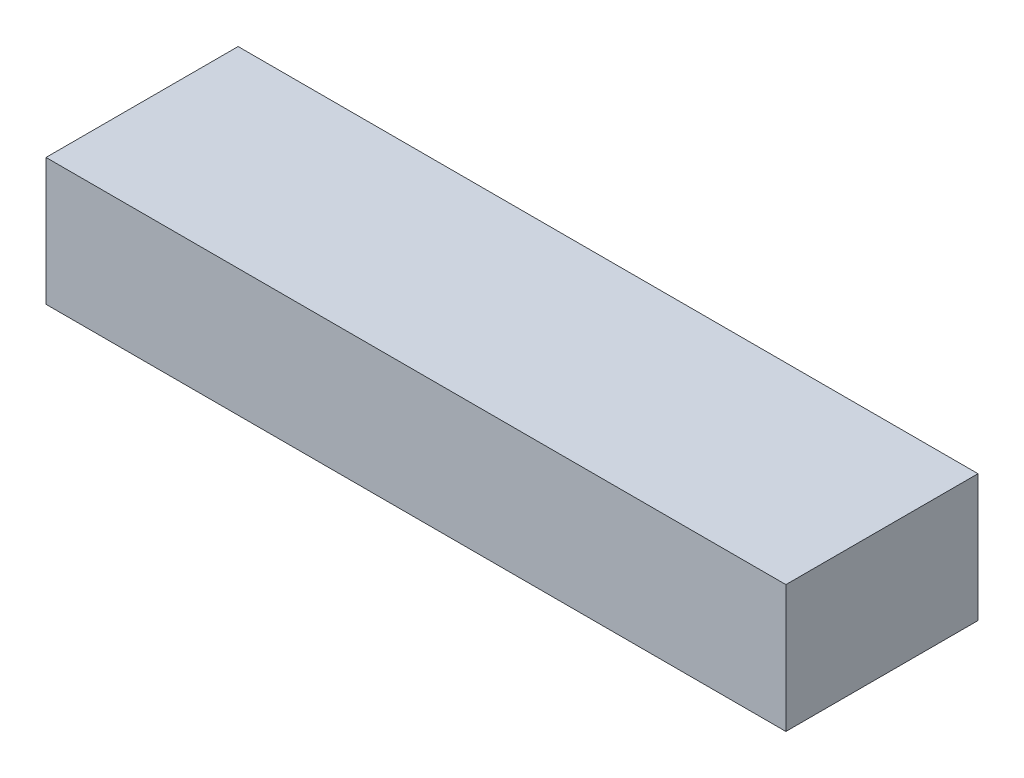
SolidWorks part; units mm, degrees
ref_plane "Front Plane" through (0, 0, 0) normal (0, 0, 1) x (1, 0, 0)
ref_plane "Top Plane" through (0, 0, 0) normal (0, 1, 0) x (1, 0, 0)
ref_plane "Right Plane" through (0, 0, 0) normal (1, 0, 0) x (0, 0, -1)
sketch "Sketch1" plane through (0, 0, 0) normal (0, 1, 0) x (1, 0, 0)
  line L1 (570, -148) -> (-570, -148)
  line L2 (570, -148) -> (570, 148)
  line L3 (570, 148) -> (-570, 148)
  line L4 (-570, -148) -> (-570, 148)
  line L5 (570, -148) -> (-570, 148) construction
  line L6 (570, 148) -> (-570, -148) construction
  point P0 (0, 0)
  dimension "D1" = 1140
  dimension "D2" = 296
extrude "Boss-Extrude1" add sketch "Sketch1" along normal blind 196
equation "\"assembly\"= 0"
equation "\"thickness 1\" = 2"
equation "\"thickness 2\" = 8"
equation "\"connecting flange\" = 35"
equation "\"main\"= 0"
equation "\"main length\" = 1200"
equation "\"main width\" = 1200"
equation "\"divider panel distance offset\" = 296"
equation "\"side panel\"= 0"
equation "\"access hatch length\" = 600"
equation "\"access hatch width\" = 450"
equation "\"access hatch offset X\" = 100"
equation "\"access hatch offset Y\" = 100"
equation "\"side panel length\" = 1200"
equation "\"side panel width\" = 950"
equation "\"back panel\"= 0"
equation "\"back panel access hatch length\" = 1150"
equation "\"back panel access hatch width\" = 206"
equation "\"back panel access hatch flange\" = 40"
equation "\"drift eliminator\"= 0"
equation "\"drift eliminator size offset\" = 10"
equation "\"drift eliminator length\" = \"back panel access hatch length\" - \"drift eliminator size offset\""
equation "\"drift eliminator width\" = \"back panel access hatch width\" - \"drift eliminator size offset\""
equation "\"drift eliminator depth\" = \"divider panel distance offset\""
equation "\"sump\" = 0"
equation "\"D1@Boss-Extrude1\"=\"drift eliminator width\""
equation "\"D1@Sketch1\"=\"drift eliminator length\""
equation "\"D2@Sketch1\"=\"drift eliminator depth\""
